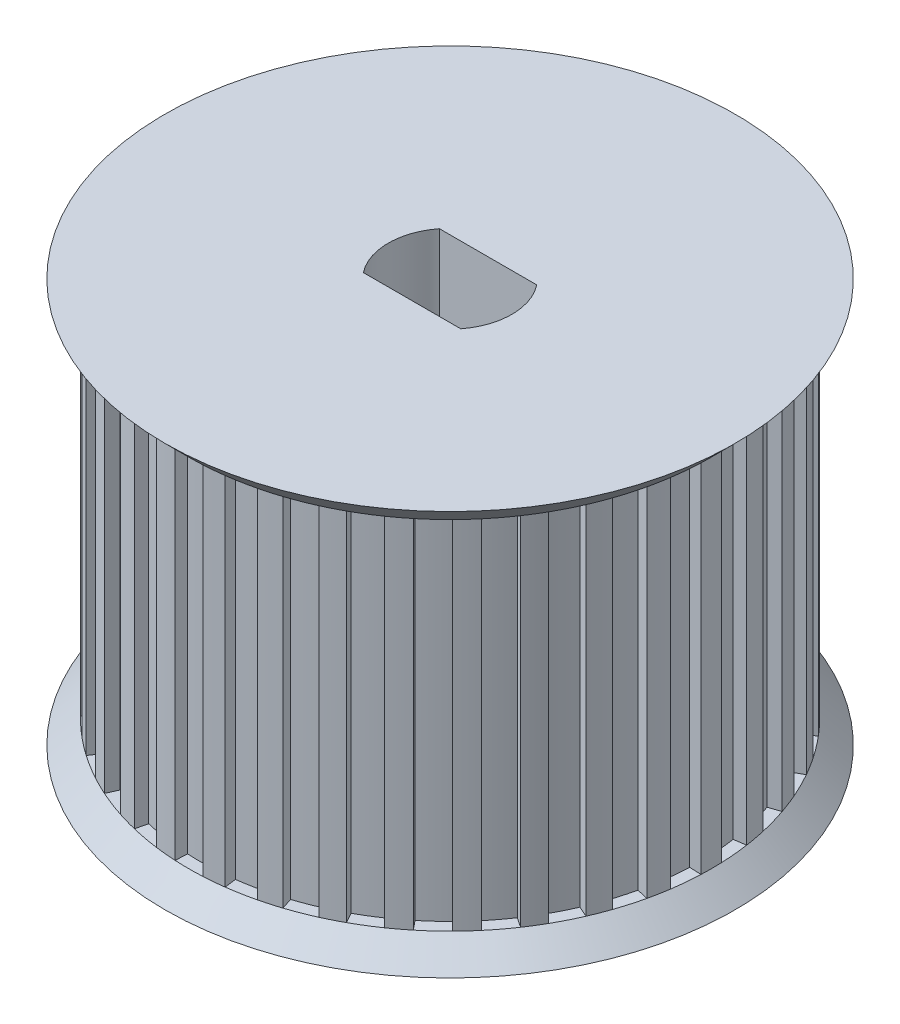
SolidWorks part; units mm, degrees
ref_plane "前视基准面" through (0, 0, 0) normal (0, 0, 1) x (1, 0, 0)
ref_plane "上视基准面" through (0, 0, 0) normal (0, 1, 0) x (1, 0, 0)
ref_plane "右视基准面" through (0, 0, 0) normal (1, 0, 0) x (0, 0, -1)
sketch "Sketch1" plane through (0, 0, 0) normal (0, 1, 0) x (1, 0, 0)
  circle A0 centre (0, 0) radius 12
  dimension "D1" = 24
extrude "Boss-Extrude1" add sketch "Sketch1" along normal blind 1
sketch "Sketch2" plane through (0, 1, 0) normal (0, 1, 0) x (1, 0, 0)
  circle A0 centre (0, 0) radius 11
  circle A2 centre (0, 0) radius 12 construction
  dimension "D1" = 1
extrude "Boss-Extrude2" add sketch "Sketch2" along normal blind 15
sketch "Sketch3" plane through (0, 16, 0) normal (0, 1, 0) x (1, 0, 0)
  circle A0 centre (0, 0) radius 12
  circle A1 centre (0, 0) radius 11 construction
  dimension "D1" = 1
extrude "Boss-Extrude3" add sketch "Sketch3" along normal blind 1
chamfer "Chamfer1" distance 1 distance2 1 2 edges at (0, 1, 12) (0, 16, 12)
sketch "Sketch4" plane through (0, 0, 0) normal (0, 1, 0) x (1, 0, 0)
  line L0 (0, 0) -> (2.5, 0) construction
  line L1 (0, 0) -> (0, 1.6) construction
  line L2 (-2.0494, 1.6) -> (2.0494, 1.6)
  line L3 (-2.0494, -1.6) -> (2.0494, -1.6)
  circle A0 centre (0, 0) radius 2.6 construction
  arc A1 (-2.0494, 1.6) -> (-2.0494, -1.6) centre (0, 0) ccw
  arc A2 (2.0494, 1.6) -> (2.0494, -1.6) centre (0, 0) cw
  dimension "D1" = 5.2
  dimension "D2" = 1.6
extrude "Cut-Extrude3" cut sketch "Sketch4" along normal up to next
sketch "Sketch7" plane through (0, 17, 0) normal (0, 1, 0) x (1, 0, 0)
  line L0 (0, 0) -> (0, 11) construction
  line L1 (0.5867, 10.9843) -> (0.56, 10.4851)
  line L2 (-0.5867, 10.9843) -> (-0.56, 10.4851)
  circle A0 centre (0, 0) radius 11 construction
  circle A1 centre (0, 0) radius 12 construction
  circle A2 centre (0, 0) radius 10.5 construction
  arc A3 (-0.5867, 10.9843) -> (0.5867, 10.9843) centre (0, 0) cw
  arc A4 (-0.56, 10.4851) -> (0.56, 10.4851) centre (0, 0) cw
  dimension "D1" = 1
  dimension "D2" = 0.5
  dimension "D3" = 1.12
extrude "Cut-Extrude5" cut sketch "Sketch7" against normal offset from surface (15 mm away) 1 from offset 1 up to face at (0, 0, 12) offset against normal yes
pattern_circular "CirPattern3" count 34 over 360 about axis through (0, 17, 0) along (0, 1, 0) of "Cut-Extrude5"
